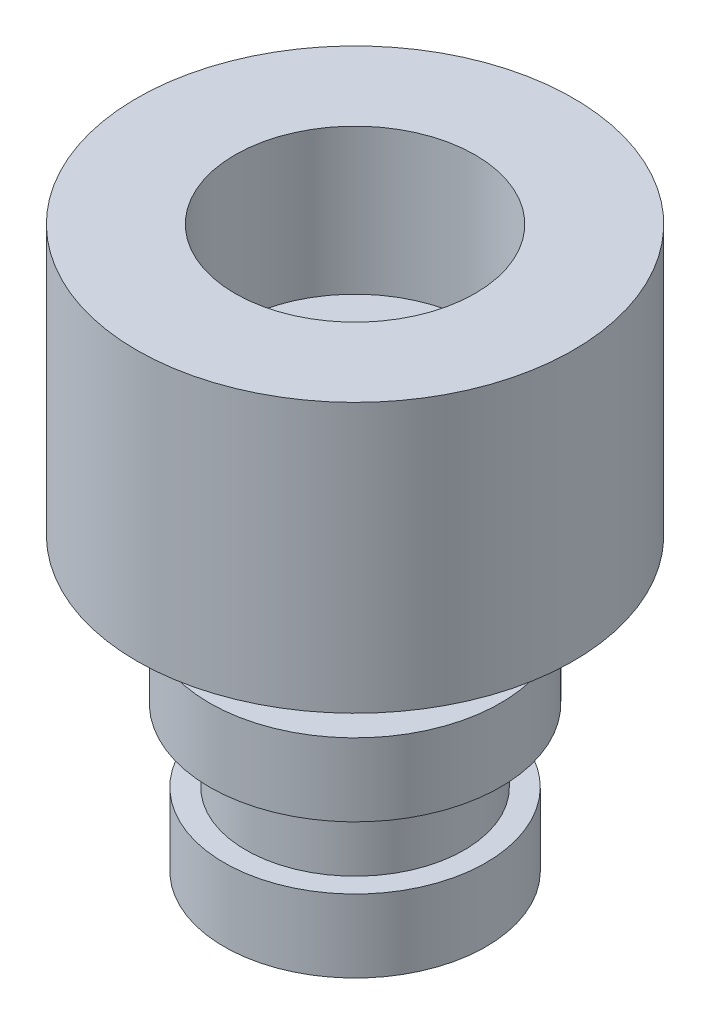
SolidWorks part; units mm, degrees
ref_plane "Front Plane" through (0, 0, 0) normal (0, 0, 1) x (1, 0, 0)
ref_plane "Top Plane" through (0, 0, 0) normal (0, 1, 0) x (1, 0, 0)
ref_plane "Right Plane" through (0, 0, 0) normal (1, 0, 0) x (0, 0, -1)
sketch "Sketch1" plane through (0, 0, 0) normal (0, 1, 0) x (1, 0, 0)
  circle A0 centre (-0.522, 0.5111) radius 1.6
  circle A1 centre (-0.522, 0.5111) radius 3
  dimension "D1" = 3.2
  dimension "D2" = 6
extrude "Boss-Extrude1" add sketch "Sketch1" along normal blind 3.7 contours A1
extrude "Boss-Extrude2" add sketch "Sketch1<3>" along normal blind 1 contours A0 region at (-0.522, 0, -0.5111)
sketch "Sketch1<3>" plane through (0, 0, 0) normal (0, 1, 0) x (1, 0, 0) same geometry as "Sketch1"
sketch "Sketch5" plane through (0, 0, 0) normal (0, -1, 0) x (1, 0, 0)
  circle A2 centre (-0.522, -0.5111) radius 1.5
  circle A3 centre (-0.522, -0.5111) radius 1.5
  dimension "D2" = 3
  dimension "D1" = 1.5
extrude "Boss-Extrude3" add sketch "Sketch5" along normal blind 1 contours A3
sketch "Sketch6" plane through (0, -1, 0) normal (0, -1, 0) x (1, 0, 0)
  circle A0 centre (-0.522, -0.5111) radius 2
  dimension "D1" = 4
extrude "Boss-Extrude4" add sketch "Sketch6" along normal blind 1
sketch "Sketch8" plane through (0, -2, 0) normal (0, -1, 0) x (-1, 0, 0)
  circle A0 centre (0.522, 0.5111) radius 1.5
  dimension "D1" = 3
extrude "Boss-Extrude5" add sketch "Sketch8" along normal blind 2 contours A0
sketch "Sketch10" plane through (0, -4, 0) normal (0, -1, 0) x (1, 0, 0)
  circle A0 centre (-0.522, -0.5111) radius 1.8
extrude "Boss-Extrude6" add sketch "Sketch10" against normal blind 1
sketch "Sketch11" plane through (0, 3.7, 0) normal (0, 1, 0) x (1, 0, 0)
  text T0 "VIII" font "Century Gothic" height in points 5
sketch "Sketch12" plane through (0, 3.7, 0) normal (0, 1, 0) x (1, 0, 0)
  circle A0 centre (-0.522, 0.5111) radius 1.65
extrude "Cut-Extrude1" cut sketch "Sketch12" against normal blind 2
